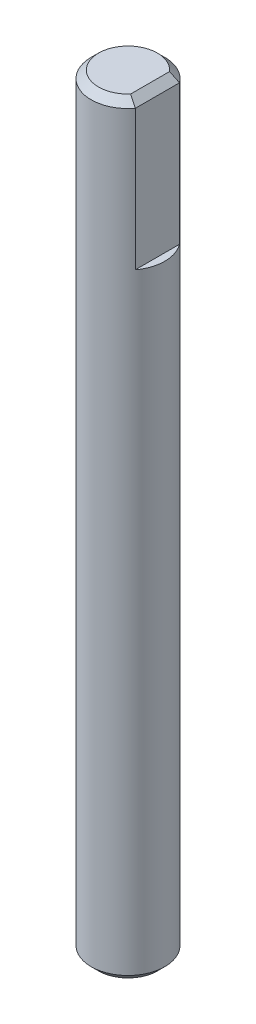
SolidWorks part; units mm, degrees
ref_plane "Front Plane" through (0, 0, 0) normal (0, 0, 1) x (1, 0, 0)
ref_plane "Top Plane" through (0, 0, 0) normal (0, 1, 0) x (1, 0, 0)
ref_plane "Right Plane" through (0, 0, 0) normal (1, 0, 0) x (0, 0, -1)
sketch "Sketch1" plane through (0, 0, 0) normal (0, 1, 0) x (1, 0, 0)
  circle A0 centre (0, 0) radius 2.5
  dimension "D1" = 5
extrude "Boss-Extrude1" add sketch "Sketch1" along normal mid plane 52
sketch "Sketch2" plane through (0, 0, 0) normal (1, 0, 0) x (0, 0, -1)
  line L0 (2.5, 26) -> (-2.5, 26) construction
  line L1 (-6.9864, 16) -> (6.9864, 16)
  line L2 (-6.9864, 16) -> (-6.9864, 30.1934)
  line L3 (-6.9864, 30.1934) -> (6.9864, 30.1934)
  line L4 (6.9864, 16) -> (6.9864, 30.1934)
  line L5 (-6.9864, 16) -> (6.9864, 30.1934) construction
  line L6 (-6.9864, 30.1934) -> (6.9864, 16) construction
  point P0 (0, 23.0967)
  point P7 (0, 0)
  dimension "D1" = 10
extrude "Cut-Extrude1" cut sketch "Sketch2" along normal blind 52 from offset 2
chamfer "Chamfer1" distance 0.5 angle 45 3 edges at (0, -26, 2.5) (-2.5, 26, 0) (2, 26, 0)
